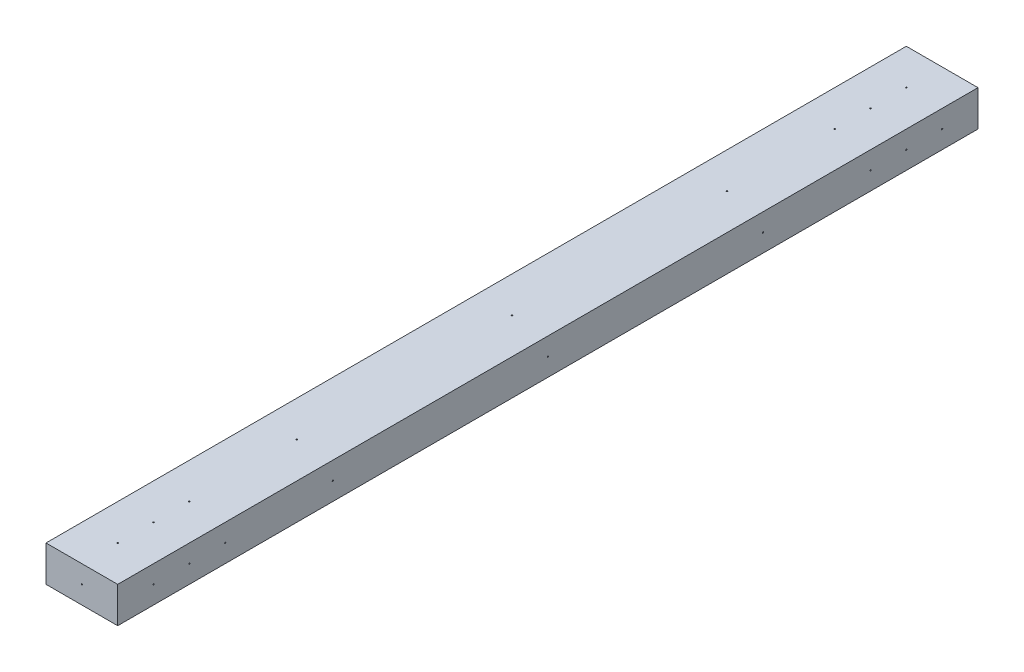
SolidWorks part; units mm, degrees
material "Pine"
ref_plane "Front Plane" through (0, 0, 0) normal (0, 0, 1) x (1, 0, 0)
ref_plane "Top Plane" through (0, 0, 0) normal (0, 1, 0) x (1, 0, 0)
ref_plane "Right Plane" through (0, 0, 0) normal (1, 0, 0) x (0, 0, -1)
sketch "Sketch1" plane through (0, 0, 0) normal (0, 0, 1) x (1, 0, 0)
  line L1 (0, 0) -> (101.6, 0)
  line L2 (0, 0) -> (0, 50.8)
  line L3 (0, 50.8) -> (101.6, 50.8)
  line L4 (101.6, 0) -> (101.6, 50.8)
  dimension "D1" = 101.6
  dimension "D2" = 50.8
extrude "Boss-Extrude1" add sketch "Sketch1" along normal blind 1219.2
sketch "Sketch2" plane through (0, 50.8, 0) normal (0, 1, 0) x (1, 0, 0)
  line L0 (50.8, 0) -> (50.8, -304.8) construction
  line L1 (101.6, 0) -> (0, 0) construction
  line L2 (0, 0) -> (0, -1219.2)
  circle A0 centre (50.8, -304.8) radius 0.8763
  dimension "D2" = 1.7526
  dimension "D1" = 304.8
extrude "Cut-Extrude1" cut sketch "Sketch2" against normal up to surface (50.8 mm away) contours A0 region at (50.8, 50.8, 304.8) up to face at (50.8, 0, 609.6)
pattern_linear "LPattern1" count 3 spacing 304.8 along (0, 0, 1) of "Cut-Extrude1"
sketch "Sketch3" plane through (0, 50.8, 0) normal (0, 1, 0) x (1, 0, 0)
  line L0 (50.8, 0) -> (50.8, -50.8) construction
  line L1 (101.6, 0) -> (0, 0) construction
  line L2 (101.6, -609.6) -> (0, -609.6) construction
  line L3 (101.6, -1219.2) -> (101.6, 0) construction
  line L4 (0, -1219.2) -> (0, 0) construction
  circle A0 centre (50.8, -50.8) radius 0.8763
  circle A1 centre (50.8, -1066.8) radius 0.8763
  circle A2 centre (50.8, -101.6) radius 0.8763
  circle A3 centre (50.8, -152.4) radius 0.8763
  circle A4 centre (50.8, -1117.6) radius 0.8763
  circle A5 centre (50.8, -1168.4) radius 0.8763
  dimension "D2" = 1.7526
  dimension "D1" = 50.8
  dimension "D3" = 3
extrude "Cut-Extrude2" cut sketch "Sketch3" against normal up to surface (50.8 mm away) up to face at (50.8, 0, 915.2763)
sketch "Sketch4" plane through (0, 0, 1219.2) normal (0, 0, 1) x (1, 0, 0)
  line L0 (0, 50.8) -> (101.6, 0) construction
  line L1 (101.6, 50.8) -> (0, 0) construction
  circle A0 centre (50.8, 25.4) radius 0.8763
  dimension "D1" = 1.7526
extrude "Cut-Extrude3" cut sketch "Sketch4" against normal up to surface (1219.2 mm away) up to face at (50.8, 25.4, 0)
sketch "Sketch6" plane through (0, 0, 0) normal (-1, 0, 0) x (0, 0, 1)
  line L0 (0, 25.4) -> (304.8, 25.4) construction
  line L1 (0, 50.8) -> (0, 0) construction
  circle A0 centre (304.8, 25.4) radius 0.8763
  circle A1 centre (609.6, 25.4) radius 0.8763
  circle A2 centre (914.4, 25.4) radius 0.8763
  dimension "D2" = 1.7526
  dimension "D1" = 304.8
  dimension "D3" = 3
extrude "Cut-Extrude4" cut sketch "Sketch6" against normal up to surface (101.6 mm away) up to face at (101.6, 25.4, 609.6)
sketch "Sketch7" plane through (0, 0, 0) normal (-1, 0, 0) x (0, 0, 1)
  line L0 (0, 25.4) -> (50.8, 25.4) construction
  line L1 (0, 50.8) -> (0, 0) construction
  line L2 (609.6, 0) -> (609.6, 50.8) construction
  line L3 (1219.2, 0) -> (0, 0) construction
  line L4 (1219.2, 50.8) -> (0, 50.8) construction
  circle A0 centre (50.8, 25.4) radius 0.8763
  circle A1 centre (101.6, 25.4) radius 0.8763
  circle A2 centre (152.4, 25.4) radius 0.8763
  circle A3 centre (1066.8, 25.4) radius 0.8763
  circle A4 centre (1117.6, 25.4) radius 0.8763
  circle A5 centre (1168.4, 25.4) radius 0.8763
  dimension "D1" = 1.7526
  dimension "D2" = 50.8
  dimension "D3" = 3
extrude "Cut-Extrude5" cut sketch "Sketch7" against normal up to surface (101.6 mm away) up to face at (101.6, 25.4, 610.4763)
equation "\"length\"= 1219.2"
equation "\"D1@Boss-Extrude1\"=\"length\""
equation "\"D1@LPattern1\" = \"length\" / 304.8 - 1"
equation "\"D3@Sketch6\"=\"length\" / 304.8 - 1"
